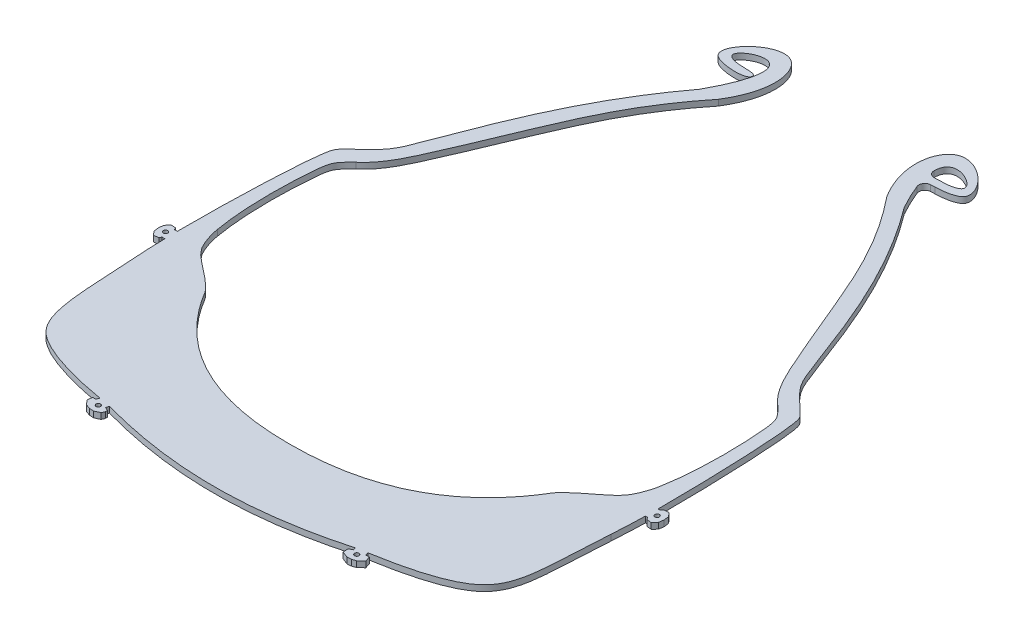
SolidWorks part; units mm, degrees
ref_plane "Front Plane" through (0, 0, 0) normal (0, 0, 1) x (1, 0, 0)
ref_plane "Top Plane" through (0, 0, 0) normal (0, 1, 0) x (1, 0, 0)
ref_plane "Right Plane" through (0, 0, 0) normal (1, 0, 0) x (0, 0, -1)
sketch "Sketch1" plane through (0, 0, 0) normal (0, 1, 0) x (1, 0, 0)
  line L0 (-56.7342, 4649.685) -> (-54.3432, 4649.8666)
  line L1 (-54.3432, 4649.8666) -> (-51.9673, 4650.1279)
  line L2 (-51.9673, 4650.1279) -> (-49.6128, 4650.4904)
  line L3 (-49.6128, 4650.4904) -> (-47.2873, 4650.9763)
  line L4 (-47.2873, 4650.9763) -> (-45.0028, 4651.606)
  line L5 (-45.0028, 4651.606) -> (-42.7754, 4652.393)
  line L6 (-42.7754, 4652.393) -> (-40.6236, 4653.3398)
  line L7 (-40.6236, 4653.3398) -> (-38.5569, 4654.4471)
  line L8 (-38.5569, 4654.4471) -> (-36.5628, 4655.7048)
  line L9 (-36.5628, 4655.7048) -> (-34.628, 4657.0886)
  line L10 (-34.628, 4657.0886) -> (-32.7572, 4658.5809)
  line L11 (-32.7572, 4658.5809) -> (-31.8781, 4659.3559)
  line L12 (-31.8781, 4659.3559) -> (-31.0378, 4660.1663)
  line L13 (-31.0378, 4660.1663) -> (-30.2434, 4661.0133)
  line L14 (-30.2434, 4661.0133) -> (-29.4929, 4661.8977)
  line L15 (-29.4929, 4661.8977) -> (-28.0377, 4663.8002)
  line L16 (-28.0377, 4663.8002) -> (-26.6418, 4665.7643)
  line L17 (-26.6418, 4665.7643) -> (-25.2842, 4667.7433)
  line L18 (-25.2842, 4667.7433) -> (-24.5616, 4668.7671)
  line L19 (-24.5616, 4668.7671) -> (-24.1207, 4669.3049)
  line L20 (-24.1207, 4669.3049) -> (-23.6287, 4669.8041)
  line L21 (-23.6287, 4669.8041) -> (-22.6527, 4670.6453)
  line L22 (-22.6527, 4670.6453) -> (-21.6624, 4671.4168)
  line L23 (-21.6624, 4671.4168) -> (-19.7154, 4672.8766)
  line L24 (-19.7154, 4672.8766) -> (-18.7888, 4673.6051)
  line L25 (-18.7888, 4673.6051) -> (-17.9151, 4674.3646)
  line L26 (-17.9151, 4674.3646) -> (-17.0961, 4675.1711)
  line L27 (-17.0961, 4675.1711) -> (-16.3332, 4676.0235)
  line L28 (-16.3332, 4676.0235) -> (-14.888, 4677.8872)
  line L29 (-14.888, 4677.8872) -> (-14.2651, 4678.8282)
  line L30 (-14.2651, 4678.8282) -> (-13.7395, 4679.8092)
  line L31 (-13.7395, 4679.8092) -> (-13.3157, 4680.8364)
  line L32 (-13.3157, 4680.8364) -> (-12.9921, 4681.9053)
  line L33 (-12.9921, 4681.9053) -> (-12.765, 4683.0137)
  line L34 (-12.765, 4683.0137) -> (-12.6116, 4684.156)
  line L35 (-12.6116, 4684.156) -> (-12.4221, 4686.5439)
  line L36 (-12.4221, 4686.5439) -> (-12.3049, 4688.9547)
  line L37 (-12.3049, 4688.9547) -> (-12.23, 4691.3606)
  line L38 (-12.23, 4691.3606) -> (-12.2173, 4693.7469)
  line L39 (-12.2173, 4693.7469) -> (-12.2979, 4696.128)
  line L40 (-12.2979, 4696.128) -> (-12.4621, 4698.525)
  line L41 (-12.4621, 4698.525) -> (-12.9016, 4703.3562)
  line L42 (-12.9016, 4703.3562) -> (-13.1725, 4705.7323)
  line L43 (-13.1725, 4705.7323) -> (-13.359, 4706.8497)
  line L44 (-13.359, 4706.8497) -> (-13.6464, 4707.8976)
  line L45 (-13.6464, 4707.8976) -> (-13.8331, 4708.3435)
  line L46 (-13.8331, 4708.3435) -> (-14.0727, 4708.7863)
  line L47 (-14.0727, 4708.7863) -> (-14.3603, 4709.2104)
  line L48 (-14.3603, 4709.2104) -> (-14.6922, 4709.6118)
  line L49 (-14.6922, 4709.6118) -> (-15.5352, 4710.4427)
  line L50 (-15.5352, 4710.4427) -> (-16.4733, 4711.2489)
  line L51 (-16.4733, 4711.2489) -> (-18.3969, 4712.8768)
  line L52 (-18.3969, 4712.8768) -> (-19.3317, 4713.7593)
  line L53 (-19.3317, 4713.7593) -> (-19.7964, 4714.2738)
  line L54 (-19.7964, 4714.2738) -> (-20.226, 4714.8564)
  line L55 (-20.226, 4714.8564) -> (-20.8491, 4716.0227)
  line L56 (-20.8491, 4716.0227) -> (-21.3607, 4717.2182)
  line L57 (-21.3607, 4717.2182) -> (-22.2565, 4719.6128)
  line L58 (-22.2565, 4719.6128) -> (-23.9365, 4724.4003)
  line L59 (-23.9365, 4724.4003) -> (-24.8142, 4726.6925)
  line L60 (-24.8142, 4726.6925) -> (-25.7235, 4728.951)
  line L61 (-25.7235, 4728.951) -> (-29.4192, 4737.978)
  line L62 (-29.4192, 4737.978) -> (-31.3112, 4742.476)
  line L63 (-31.3112, 4742.476) -> (-32.3108, 4744.6883)
  line L64 (-32.3108, 4744.6883) -> (-33.3653, 4746.8748)
  line L65 (-33.3653, 4746.8748) -> (-34.484, 4749.0197)
  line L66 (-34.484, 4749.0197) -> (-35.6822, 4751.1089)
  line L67 (-35.6822, 4751.1089) -> (-36.9697, 4753.1376)
  line L68 (-36.9697, 4753.1376) -> (-38.335, 4755.1176)
  line L69 (-38.335, 4755.1176) -> (-39.7566, 4757.0561)
  line L70 (-39.7566, 4757.0561) -> (-41.2239, 4758.9538)
  line L71 (-41.2239, 4758.9538) -> (-44.2837, 4762.6862)
  line L72 (-44.2837, 4762.6862) -> (-45.0093, 4763.5782)
  line L73 (-45.7102, 4766.0333) -> (-45.6003, 4766.895)
  line L74 (-44.3387, 4767.2717) -> (-41.5099, 4763.9631)
  line L75 (-41.5099, 4763.9631) -> (-39.7615, 4761.7893)
  line L76 (-39.7615, 4761.7893) -> (-36.1552, 4757.1077)
  line L77 (-36.1552, 4757.1077) -> (-34.4224, 4754.6956)
  line L78 (-34.4224, 4754.6956) -> (-32.818, 4752.1875)
  line L79 (-32.818, 4752.1875) -> (-31.4001, 4749.5854)
  line L80 (-31.4001, 4749.5854) -> (-30.1172, 4746.945)
  line L81 (-30.1172, 4746.945) -> (-27.7453, 4741.6402)
  line L82 (-27.7453, 4741.6402) -> (-25.4835, 4736.2816)
  line L83 (-25.4835, 4736.2816) -> (-23.2904, 4730.8724)
  line L84 (-23.2904, 4730.8724) -> (-21.1708, 4725.4153)
  line L85 (-21.1708, 4725.4153) -> (-19.1018, 4719.943)
  line L86 (-19.1018, 4719.943) -> (-18.1004, 4717.2034)
  line L87 (-18.1004, 4717.2034) -> (-17.875, 4716.5966)
  line L88 (-17.875, 4716.5966) -> (-17.6236, 4716.1359)
  line L89 (-17.6236, 4716.1359) -> (-17.2675, 4715.7336)
  line L90 (-17.2675, 4715.7336) -> (-16.7845, 4715.2999)
  line L91 (-16.7845, 4715.2999) -> (-14.566, 4713.4273)
  line L92 (-14.566, 4713.4273) -> (-13.4359, 4712.453)
  line L93 (-13.4359, 4712.453) -> (-12.2875, 4711.3506)
  line L94 (-12.2875, 4711.3506) -> (-11.7288, 4710.5494)
  line L95 (-11.7288, 4710.5494) -> (-11.4049, 4709.6505)
  line L96 (-11.4049, 4709.6505) -> (-11.1035, 4708.0976)
  line L97 (-11.1035, 4708.0976) -> (-10.7039, 4705.1867)
  line L98 (-10.7039, 4705.1867) -> (-10.3782, 4702.2301)
  line L99 (-10.3782, 4702.2301) -> (-10.1381, 4699.312)
  line L100 (-10.1381, 4699.312) -> (-9.9526, 4696.4059)
  line L101 (-9.9526, 4696.4059) -> (-9.8234, 4693.4642)
  line L102 (-9.8234, 4693.4642) -> (-9.7818, 4690.5097)
  line L103 (-9.7818, 4690.5097) -> (-9.8395, 4687.5651)
  line L104 (-9.8395, 4687.5651) -> (-10.1467, 4681.8499)
  line L105 (-10.2187, 4680.4106) -> (-10.5778, 4674.8324)
  line L106 (-10.5778, 4674.8324) -> (-10.9255, 4669.1921)
  line L107 (-10.9255, 4669.1921) -> (-11.1085, 4666.3239)
  line L108 (-11.1085, 4666.3239) -> (-11.3672, 4663.3976)
  line L109 (-11.3672, 4663.3976) -> (-11.5954, 4661.8877)
  line L110 (-11.5954, 4661.8877) -> (-11.9481, 4660.3817)
  line L111 (-11.9481, 4660.3817) -> (-12.469, 4658.9063)
  line L112 (-12.469, 4658.9063) -> (-13.1768, 4657.5086)
  line L113 (-13.1768, 4657.5086) -> (-14.0475, 4656.2056)
  line L114 (-14.0475, 4656.2056) -> (-15.0678, 4655.0233)
  line L115 (-15.0678, 4655.0233) -> (-15.6664, 4654.4674)
  line L116 (-15.6664, 4654.4674) -> (-16.3022, 4653.9611)
  line L117 (-16.3022, 4653.9611) -> (-17.6055, 4653.1269)
  line L118 (-17.6055, 4653.1269) -> (-18.9712, 4652.4383)
  line L119 (-18.9712, 4652.4383) -> (-20.3502, 4651.8561)
  line L120 (-20.3502, 4651.8561) -> (-21.7405, 4651.3486)
  line L121 (-21.7405, 4651.3486) -> (-23.1491, 4650.8937)
  line L122 (-23.1491, 4650.8937) -> (-25.9685, 4650.1281)
  line L123 (-25.9685, 4650.1281) -> (-28.8127, 4649.495)
  line L124 (-28.8127, 4649.495) -> (-34.3611, 4648.4388)
  line L125 (-35.7786, 4648.1905) -> (-42.1243, 4647.1501)
  line L126 (-42.1243, 4647.1501) -> (-45.3893, 4646.7207)
  line L127 (-45.3893, 4646.7207) -> (-48.6635, 4646.3827)
  line L128 (-48.6635, 4646.3827) -> (-55.1892, 4645.922)
  line L129 (-55.1892, 4645.922) -> (-61.7354, 4645.5886)
  line L130 (-61.7354, 4645.5886) -> (-63.9666, 4645.5453)
  line L131 (-63.9667, 4649.4865) -> (-59.1315, 4649.5688)
  line L132 (-59.1315, 4649.5688) -> (-56.7342, 4649.685)
  line L133 (-9.7721, 4681.8294) -> (-9.752, 4682.186)
  line L134 (-9.752, 4682.186) -> (-9.3693, 4682.5229)
  line L135 (-9.3693, 4682.5229) -> (-8.649, 4682.4768)
  line L136 (-8.649, 4682.4768) -> (-7.9775, 4681.713)
  line L137 (-7.9775, 4681.713) -> (-8.2411, 4680.2884)
  line L138 (-8.2411, 4680.2884) -> (-9.0059, 4679.6162)
  line L139 (-9.0059, 4679.6162) -> (-9.5491, 4679.6473)
  line L140 (-9.5491, 4679.6473) -> (-9.8867, 4680.0303)
  line L141 (-9.8867, 4680.0303) -> (-9.8664, 4680.3889)
  line L142 (-9.7721, 4681.8294) -> (-9.752, 4682.186)
  line L151 (-34.2991, 4648.0806) -> (-33.9447, 4648.1421)
  line L152 (-33.9447, 4648.1421) -> (-33.5285, 4647.8485)
  line L153 (-33.5285, 4647.8485) -> (-33.4056, 4647.1395)
  line L154 (-33.4056, 4647.1395) -> (-33.9931, 4646.3074)
  line L155 (-33.9931, 4646.3074) -> (-35.4108, 4646.0612)
  line L156 (-35.4108, 4646.0612) -> (-36.2441, 4646.6493)
  line L157 (-36.2441, 4646.6493) -> (-36.3669, 4647.358)
  line L158 (-36.3669, 4647.358) -> (-36.0733, 4647.7743)
  line L159 (-36.0733, 4647.7743) -> (-35.7187, 4647.8357)
  line L160 (-10.1467, 4681.8499) -> (-9.7721, 4681.8294)
  line L161 (-34.3611, 4648.4388) -> (-34.2991, 4648.0806)
  line L162 (-35.7786, 4648.1905) -> (-35.7187, 4647.8357)
  line L163 (-9.8664, 4680.3889) -> (-10.2187, 4680.4106)
  line L165 (-118.1813, 4682.186) -> (-118.5641, 4682.5226)
  line L166 (-118.5641, 4682.5226) -> (-119.2843, 4682.4768)
  line L167 (-119.2843, 4682.4768) -> (-119.9558, 4681.7128)
  line L168 (-119.9558, 4681.7128) -> (-119.8643, 4680.2786)
  line L169 (-119.8643, 4680.2786) -> (-119.0995, 4679.6064)
  line L170 (-119.0995, 4679.6064) -> (-118.3843, 4679.6471)
  line L171 (-118.3843, 4679.6471) -> (-118.0466, 4680.0303)
  line L172 (-118.0466, 4680.0303) -> (-118.0672, 4680.3889)
  line L173 (-118.0672, 4680.3889) -> (-117.7148, 4680.4103)
  line L174 (-117.7148, 4680.4103) -> (-117.3555, 4674.8322)
  line L175 (-117.3555, 4674.8322) -> (-117.0078, 4669.1921)
  line L176 (-117.0078, 4669.1921) -> (-116.8249, 4666.3237)
  line L177 (-116.8249, 4666.3237) -> (-116.566, 4663.3974)
  line L178 (-116.566, 4663.3974) -> (-116.3378, 4661.8875)
  line L179 (-116.3378, 4661.8875) -> (-115.9851, 4660.3817)
  line L180 (-115.9851, 4660.3817) -> (-115.4645, 4658.906)
  line L181 (-115.4645, 4658.906) -> (-114.7563, 4657.5086)
  line L182 (-114.7563, 4657.5086) -> (-113.8857, 4656.2053)
  line L183 (-113.8857, 4656.2053) -> (-112.8656, 4655.0233)
  line L184 (-112.8656, 4655.0233) -> (-112.2669, 4654.4674)
  line L185 (-112.2669, 4654.4674) -> (-111.6311, 4653.9608)
  line L186 (-111.6311, 4653.9608) -> (-110.328, 4653.1269)
  line L187 (-110.328, 4653.1269) -> (-108.9621, 4652.4383)
  line L188 (-108.9621, 4652.4383) -> (-107.5832, 4651.8561)
  line L189 (-107.5832, 4651.8561) -> (-106.1928, 4651.3484)
  line L190 (-106.1928, 4651.3484) -> (-104.7844, 4650.8937)
  line L191 (-104.7844, 4650.8937) -> (-101.9649, 4650.1279)
  line L192 (-101.9649, 4650.1279) -> (-99.1205, 4649.4948)
  line L193 (-99.1205, 4649.4948) -> (-93.5721, 4648.4388)
  line L194 (-93.5721, 4648.4388) -> (-93.6341, 4648.0806)
  line L195 (-93.6341, 4648.0806) -> (-93.9885, 4648.1421)
  line L196 (-93.9885, 4648.1421) -> (-94.4046, 4647.8485)
  line L197 (-94.4046, 4647.8485) -> (-94.5276, 4647.1392)
  line L198 (-94.5276, 4647.1392) -> (-93.9404, 4646.3074)
  line L199 (-93.9404, 4646.3074) -> (-92.5223, 4646.0612)
  line L200 (-92.5223, 4646.0612) -> (-91.6891, 4646.6493)
  line L201 (-91.6891, 4646.6493) -> (-91.5662, 4647.358)
  line L202 (-91.5662, 4647.358) -> (-91.8598, 4647.7743)
  line L203 (-91.8598, 4647.7743) -> (-92.2145, 4647.8357)
  line L204 (-92.1546, 4648.1905) -> (-92.2145, 4647.8357)
  line L205 (-92.1546, 4648.1905) -> (-85.8089, 4647.1501)
  line L206 (-85.8089, 4647.1501) -> (-82.5441, 4646.7204)
  line L207 (-82.5441, 4646.7204) -> (-79.2698, 4646.3827)
  line L208 (-79.2698, 4646.3827) -> (-72.7439, 4645.922)
  line L209 (-72.7439, 4645.922) -> (-66.1978, 4645.5886)
  line L210 (-66.1978, 4645.5886) -> (-63.9666, 4645.5453)
  line L211 (-63.9667, 4649.4865) -> (-68.8018, 4649.5688)
  line L212 (-68.8018, 4649.5688) -> (-71.1991, 4649.685)
  line L213 (-71.1991, 4649.685) -> (-73.5901, 4649.8666)
  line L214 (-73.5901, 4649.8666) -> (-75.9659, 4650.1279)
  line L215 (-75.9659, 4650.1279) -> (-78.3204, 4650.4904)
  line L216 (-78.3204, 4650.4904) -> (-80.646, 4650.976)
  line L217 (-80.646, 4650.976) -> (-82.9304, 4651.606)
  line L218 (-82.9304, 4651.606) -> (-85.1578, 4652.393)
  line L219 (-85.1578, 4652.393) -> (-87.3097, 4653.3398)
  line L220 (-87.3097, 4653.3398) -> (-89.3762, 4654.4469)
  line L221 (-89.3762, 4654.4469) -> (-91.3704, 4655.7045)
  line L222 (-91.3704, 4655.7045) -> (-93.3054, 4657.0883)
  line L223 (-93.3054, 4657.0883) -> (-95.1761, 4658.5809)
  line L224 (-95.1761, 4658.5809) -> (-96.0551, 4659.3559)
  line L225 (-96.0551, 4659.3559) -> (-96.8955, 4660.1661)
  line L226 (-96.8955, 4660.1661) -> (-97.6899, 4661.013)
  line L227 (-97.6899, 4661.013) -> (-98.4405, 4661.8974)
  line L228 (-98.4405, 4661.8974) -> (-99.8956, 4663.8003)
  line L229 (-99.8956, 4663.8003) -> (-101.2917, 4665.7643)
  line L230 (-101.2917, 4665.7643) -> (-102.649, 4667.7433)
  line L231 (-102.649, 4667.7433) -> (-103.3717, 4668.7671)
  line L232 (-103.3717, 4668.7671) -> (-103.8126, 4669.3049)
  line L233 (-103.8126, 4669.3049) -> (-104.3045, 4669.8038)
  line L234 (-104.3045, 4669.8038) -> (-105.2805, 4670.645)
  line L235 (-105.2805, 4670.645) -> (-106.2711, 4671.4168)
  line L236 (-106.2711, 4671.4168) -> (-108.218, 4672.8766)
  line L237 (-108.218, 4672.8766) -> (-109.1446, 4673.6051)
  line L238 (-109.1446, 4673.6051) -> (-110.0184, 4674.3646)
  line L239 (-110.0184, 4674.3646) -> (-110.8371, 4675.1711)
  line L240 (-110.8371, 4675.1711) -> (-111.6001, 4676.0232)
  line L241 (-111.6001, 4676.0232) -> (-113.0454, 4677.8872)
  line L242 (-113.0454, 4677.8872) -> (-113.6683, 4678.8282)
  line L243 (-113.6683, 4678.8282) -> (-114.1938, 4679.8092)
  line L244 (-114.1938, 4679.8092) -> (-114.6176, 4680.8364)
  line L245 (-114.6176, 4680.8364) -> (-114.9413, 4681.905)
  line L246 (-114.9413, 4681.905) -> (-115.1684, 4683.0135)
  line L247 (-115.1684, 4683.0135) -> (-115.3218, 4684.156)
  line L248 (-115.3218, 4684.156) -> (-115.5115, 4686.5436)
  line L249 (-115.5115, 4686.5436) -> (-115.6283, 4688.9545)
  line L250 (-115.6283, 4688.9545) -> (-115.7033, 4691.3606)
  line L251 (-115.7033, 4691.3606) -> (-115.7161, 4693.7466)
  line L252 (-115.7161, 4693.7466) -> (-115.6355, 4696.1278)
  line L253 (-115.6355, 4696.1278) -> (-115.4714, 4698.525)
  line L254 (-115.4714, 4698.525) -> (-115.0316, 4703.3562)
  line L255 (-115.0316, 4703.3562) -> (-114.7608, 4705.732)
  line L256 (-114.7608, 4705.732) -> (-114.5743, 4706.8497)
  line L257 (-114.5743, 4706.8497) -> (-114.287, 4707.8977)
  line L258 (-114.287, 4707.8977) -> (-114.1002, 4708.3435)
  line L259 (-114.1002, 4708.3435) -> (-113.8608, 4708.7862)
  line L260 (-113.8608, 4708.7862) -> (-113.5731, 4709.2103)
  line L261 (-113.5731, 4709.2103) -> (-113.2411, 4709.6117)
  line L262 (-113.2411, 4709.6117) -> (-112.3981, 4710.4425)
  line L263 (-112.3981, 4710.4425) -> (-111.4599, 4711.2487)
  line L264 (-111.4599, 4711.2487) -> (-109.5364, 4712.8767)
  line L265 (-109.5364, 4712.8767) -> (-108.602, 4713.7592)
  line L266 (-108.602, 4713.7592) -> (-108.1369, 4714.2737)
  line L267 (-108.1369, 4714.2737) -> (-107.7072, 4714.8564)
  line L268 (-107.7072, 4714.8564) -> (-107.0842, 4716.0225)
  line L269 (-107.0842, 4716.0225) -> (-106.5727, 4717.2181)
  line L270 (-106.5727, 4717.2181) -> (-105.6769, 4719.6127)
  line L271 (-105.6769, 4719.6127) -> (-103.9969, 4724.4001)
  line L272 (-103.9969, 4724.4001) -> (-103.1193, 4726.6924)
  line L273 (-103.1193, 4726.6924) -> (-102.2099, 4728.9509)
  line L274 (-102.2099, 4728.9509) -> (-98.5143, 4737.9778)
  line L275 (-98.5143, 4737.9778) -> (-96.6221, 4742.4757)
  line L276 (-96.6221, 4742.4757) -> (-95.6227, 4744.6884)
  line L277 (-95.6227, 4744.6884) -> (-94.5682, 4746.8748)
  line L278 (-94.5682, 4746.8748) -> (-93.4493, 4749.0197)
  line L279 (-93.4493, 4749.0197) -> (-92.2515, 4751.1088)
  line L280 (-92.2515, 4751.1088) -> (-90.9637, 4753.1374)
  line L281 (-90.9637, 4753.1374) -> (-89.5985, 4755.1174)
  line L282 (-89.5985, 4755.1174) -> (-88.177, 4757.0561)
  line L283 (-88.177, 4757.0561) -> (-86.7094, 4758.9538)
  line L284 (-86.7094, 4758.9538) -> (-83.65, 4762.6862)
  line L285 (-83.65, 4762.6862) -> (-82.924, 4763.5782)
  line L286 (-82.2232, 4766.0334) -> (-82.3333, 4766.8949)
  line L287 (-83.5948, 4767.2716) -> (-86.4235, 4763.963)
  line L288 (-86.4235, 4763.963) -> (-88.172, 4761.7894)
  line L289 (-88.172, 4761.7894) -> (-91.7784, 4757.1074)
  line L290 (-91.7784, 4757.1074) -> (-93.5112, 4754.6958)
  line L291 (-93.5112, 4754.6958) -> (-95.1154, 4752.1875)
  line L292 (-95.1154, 4752.1875) -> (-96.5333, 4749.5852)
  line L293 (-96.5333, 4749.5852) -> (-97.8162, 4746.9449)
  line L294 (-97.8162, 4746.9449) -> (-100.1881, 4741.6403)
  line L295 (-100.1881, 4741.6403) -> (-102.4501, 4736.2814)
  line L296 (-102.4501, 4736.2814) -> (-104.6429, 4730.8726)
  line L297 (-104.6429, 4730.8726) -> (-106.7626, 4725.415)
  line L298 (-106.7626, 4725.415) -> (-108.8314, 4719.9429)
  line L299 (-108.8314, 4719.9429) -> (-109.8329, 4717.2035)
  line L300 (-109.8329, 4717.2035) -> (-110.0583, 4716.5964)
  line L301 (-110.0583, 4716.5964) -> (-110.3097, 4716.1357)
  line L302 (-110.3097, 4716.1357) -> (-110.6661, 4715.7335)
  line L303 (-110.6661, 4715.7335) -> (-111.1489, 4715.2998)
  line L304 (-111.1489, 4715.2998) -> (-113.3676, 4713.4272)
  line L305 (-113.3676, 4713.4272) -> (-114.4976, 4712.4528)
  line L306 (-114.4976, 4712.4528) -> (-115.646, 4711.3505)
  line L307 (-115.646, 4711.3505) -> (-116.2044, 4710.5493)
  line L308 (-116.2044, 4710.5493) -> (-116.5286, 4709.6504)
  line L309 (-116.5286, 4709.6504) -> (-116.8298, 4708.0975)
  line L310 (-116.8298, 4708.0975) -> (-117.2296, 4705.1868)
  line L311 (-117.2296, 4705.1868) -> (-117.5553, 4702.2301)
  line L312 (-117.5553, 4702.2301) -> (-117.7952, 4699.312)
  line L313 (-117.7952, 4699.312) -> (-117.981, 4696.4059)
  line L314 (-117.981, 4696.4059) -> (-118.11, 4693.4642)
  line L315 (-118.11, 4693.4642) -> (-118.1516, 4690.5097)
  line L316 (-118.1516, 4690.5097) -> (-118.0939, 4687.5649)
  line L317 (-118.0939, 4687.5649) -> (-117.7865, 4681.8497)
  line L318 (-117.7865, 4681.8497) -> (-118.1612, 4681.8294)
  line L319 (-118.1612, 4681.8294) -> (-118.1813, 4682.186)
  spline S0 degree 3 poles (-45.7102, 4766.0333) (-45.8224, 4765.1537) (-45.5692, 4764.2663) (-45.0093, 4763.5782) knots 0 0 0 0 1 1 1 1
  spline S1 degree 3 poles (-44.3387, 4767.2717) (-44.5973, 4767.574) (-45.0517, 4767.6095) (-45.3539, 4767.351) knots 0 0 0 0 1 1 1 1
  spline S2 degree 3 poles (-45.3539, 4767.351) (-45.4898, 4767.2349) (-45.5777, 4767.0723) (-45.6003, 4766.895) knots 0 0 0 0 1 1 1 1
  spline S3 degree 3 poles (-82.924, 4763.5782) (-82.3642, 4764.2661) (-82.111, 4765.1536) (-82.2232, 4766.0334) knots 0 0 0 0 1 1 1 1
  spline S4 degree 3 poles (-82.3333, 4766.8949) (-82.3835, 4767.2894) (-82.7441, 4767.5683) (-83.1386, 4767.518) knots 0 0 0 0 1 1 1 1
  spline S5 degree 3 poles (-83.1386, 4767.518) (-83.3159, 4767.4954) (-83.4785, 4767.4075) (-83.5948, 4767.2716) knots 0 0 0 0 1 1 1 1
sketch "Sketch2" plane through (0, 0, 0) normal (0, 1, 0) x (1, 0, 0)
  line L0 (-63.9234, 4631.4262) -> (-63.9234, 4609.4594) construction
  line L25 (-22.4985, 4637.3551) -> (-18.9434, 4638.0357) construction
  line L26 (-20.7209, 4637.6954) -> (-20.3316, 4635.6618) construction
  line L31 (-16.9423, 4635.297) -> (-18.5347, 4633.796)
  line L32 (-20.3316, 4635.6618) -> (-19.8467, 4633.1287) construction
  line L33 (-18.5347, 4633.796) -> (-19.8873, 4633.3404)
  line L34 (-21.3125, 4633.2642) -> (-19.8873, 4633.3404)
  line L35 (-23.3466, 4634.071) -> (-21.3125, 4633.2642)
  line L40 (-104.4735, 4635.7404) -> (-104.4735, 4634.9567)
  line L41 (-104.4735, 4634.9567) -> (-104.8805, 4633.998)
  line L42 (-104.8805, 4633.998) -> (-106.6203, 4633.1744)
  line L43 (-106.6203, 4633.1744) -> (-108.2043, 4633.2927)
  line L44 (-109.6975, 4633.8343) -> (-108.2043, 4633.2927)
  line L45 (-110.9466, 4635.2989) -> (-109.6975, 4633.8343)
  line L46 (-110.9246, 4636.3402) -> (-110.9466, 4635.2989)
  line L47 (-110.6737, 4637.0191) -> (-110.9246, 4636.3402)
  line L49 (-146.8202, 4697.6298) -> (-149.3915, 4697.5949) construction
  line L50 (16.9036, 4697.658) -> (18.9735, 4697.6298) construction
  line L54 (20.0716, 4700.6062) -> (21.1812, 4699.2558)
  line L55 (18.9735, 4697.6298) -> (21.5448, 4697.5949) construction
  line L56 (21.1812, 4699.2558) -> (21.376, 4697.5972)
  line L57 (21.1362, 4695.9445) -> (21.376, 4697.5972)
  line L58 (19.9903, 4694.6247) -> (21.1362, 4695.9445)
  line L62 (-144.7504, 4697.658) -> (-146.8202, 4697.6298) construction
  line L67 (-148.983, 4695.9445) -> (-149.2228, 4697.5972)
  line L68 (-149.028, 4699.2558) -> (-149.2228, 4697.5972)
  line L69 (-147.9184, 4700.6062) -> (-149.028, 4699.2558)
  line L73 (18.4279, 4700.4703) -> (20.0716, 4700.6062)
  line L74 (18.3509, 4694.8052) -> (19.9903, 4694.6247)
  line L75 (-23.4805, 4635.8657) -> (-23.3466, 4634.071)
  line L76 (-17.4807, 4637.0143) -> (-16.9423, 4635.297)
  line L77 (-32.2984, 4843.1108) -> (-32.9734, 4843.0745)
  line L78 (-30.1329, 4840.4892) -> (-31.6175, 4840.4173)
  line L79 (-146.2747, 4700.4703) -> (-146.0774, 4699.7908)
  line L80 (-146.0774, 4699.7908) -> (-144.9978, 4699.7908)
  line L81 (-146.1977, 4694.8052) -> (-145.9394, 4695.5191)
  line L82 (-145.9394, 4695.5191) -> (-144.9397, 4695.5191)
  line L83 (-110.6737, 4637.0191) -> (-109.7005, 4637.0191)
  line L84 (-109.7005, 4637.0191) -> (-109.3372, 4638.0212)
  line L85 (-104.4735, 4635.7404) -> (-105.6297, 4636.1595)
  line L86 (-105.6297, 4636.1595) -> (-105.3482, 4637.2394)
  line L87 (-23.4805, 4635.8657) -> (-22.2692, 4636.4725)
  line L88 (-22.2692, 4636.4725) -> (-22.4985, 4637.3551)
  line L89 (-17.4807, 4637.0143) -> (-18.7231, 4637.0143)
  line L90 (-18.7231, 4637.0143) -> (-18.9434, 4638.0357)
  line L91 (17.093, 4695.5191) -> (17.927, 4695.5191)
  line L92 (17.927, 4695.5191) -> (18.3509, 4694.8052)
  line L93 (17.151, 4699.7908) -> (17.9273, 4699.7908)
  line L94 (17.9273, 4699.7908) -> (18.4279, 4700.4703)
  line L95 (-147.9184, 4700.6062) -> (-146.2747, 4700.4703)
  line L96 (-148.983, 4695.9445) -> (-147.9184, 4694.6247)
  line L97 (-147.9184, 4694.6247) -> (-146.1977, 4694.8052)
  circle A0 centre (28.2666, 4698.0399) radius 0.5
  circle A1 centre (-20.3316, 4635.6618) radius 0.75
  circle A2 centre (-107.5151, 4635.6618) radius 0.75
  circle A4 centre (18.9735, 4697.6298) radius 0.75
  circle A5 centre (-146.8202, 4697.6298) radius 0.75
  arc A6 (-33.3889, 4837.7057) -> (-31.6175, 4840.4173) centre (-31.5206, 4838.4196) cw
  arc A7 (-35.0807, 4845.0881) -> (-32.9734, 4843.0745) centre (-33.0807, 4845.0716) ccw
  spline S0 degree 3 poles (-105.3482, 4637.2394) (-91.774, 4633.4496) (-63.9165, 4629.3481) (-36.075, 4633.5591) (-22.4985, 4637.3551) knots 0.018742 0.018742 0.018742 0.018742 0.500293 0.981945 0.981945 0.981945 0.981945
  spline S1 degree 3 poles (-18.9434, 4638.0357) (-9.0248, 4639.6859) (4.6467, 4643.0604) (16.372, 4654.3944) (15.2524, 4666.3346) (16.6172, 4684.5147) knots 0.018902 0.018902 0.018902 0.018902 0.394122 0.490995 0.987629 0.987629 0.987629 0.987629
  spline S2 degree 3 poles (16.6172, 4684.5147) (16.7593, 4687.5885) (17.0552, 4691.3248) (17.093, 4695.5191) knots 0.004735 0.004735 0.004735 0.004735 0.035162 0.035162 0.035162 0.035162
  spline S3 degree 3 poles (17.151, 4699.7908) (17.187, 4718.7532) (15.9463, 4748.1489) (12.9962, 4752.2096) (5.5902, 4758.1445) (-2.0809, 4776.0395) (-10.7699, 4804.5442) (-29.3841, 4829.3082) knots 0.04445 0.04445 0.04445 0.04445 0.175223 0.204985 0.326837 0.407861 1 1 1 1
  spline S4 degree 2 poles (-63.9234, 4656.5726) (-23.3221, 4656.4521) (-5.293, 4686.6697) knots 0 0 0 1 1 1
  spline S5 degree 3 poles (-5.293, 4686.6697) (-3.3882, 4689.5147) (5.5322, 4695.6316) (7.0158, 4697.627) (8.9185, 4699.9572) (10.6489, 4704.6448) (10.9298, 4707.0618) knots 0 0 0 0 0.517385 0.711984 0.762678 1 1 1 1
  spline S6 degree 3 poles (10.9298, 4707.0618) (12.5257, 4715.666) (12.951, 4730.9053) (11.2091, 4746.2487) (8.6834, 4748.7091) (7.186, 4750.111) knots 0 0 0 0 0.7977 0.8977 1 1 1 1
  spline S7 degree 3 poles (7.186, 4750.111) (2.646, 4753.9155) (-14.478, 4791.0238) (-18.8641, 4808.8265) (-35.5523, 4829.6542) knots 0 0 0 0 0.147118 0.925748 0.925748 0.925748 0.925748
  spline S8 degree 3 poles (-29.3841, 4829.3082) (-30.2798, 4830.9279) (-31.829, 4833.9406) (-32.9356, 4836.5196) (-33.3889, 4837.7057) knots 0 0 0 0 0.008449 0.016898 0.016898 0.016898 0.016898
  spline S9 degree 3 poles (-98.4627, 4829.3082) (-93.3382, 4838.5746) (-89.9132, 4854.9965) (-105.7569, 4846.1357) (-99.8483, 4842.6646) (-93.6101, 4843.6599) (-92.6055, 4839.7881) (-104.6155, 4840.3686) (-107.728, 4847.4621) (-89.6554, 4862.6974) (-85.2547, 4840.9598) (-92.2945, 4829.6542) knots 0 0 0 0 0.048335 0.142928 0.16216 0.231927 0.259382 0.409256 0.461524 0.763332 1 1 1 1
  spline S10 degree 3 poles (-135.0327, 4750.111) (-130.4928, 4753.9155) (-113.3687, 4791.0238) (-108.9827, 4808.8265) (-92.2945, 4829.6542) knots 0 0 0 0 0.147118 0.925748 0.925748 0.925748 0.925748
  spline S11 degree 3 poles (-138.7766, 4707.0618) (-140.3724, 4715.666) (-140.7978, 4730.9053) (-139.0558, 4746.2487) (-136.5302, 4748.7091) (-135.0327, 4750.111) knots 0 0 0 0 0.7977 0.8977 1 1 1 1
  spline S12 degree 3 poles (-122.5537, 4686.6697) (-124.4586, 4689.5147) (-133.3789, 4695.6316) (-134.8625, 4697.627) (-136.7653, 4699.9572) (-138.4957, 4704.6448) (-138.7766, 4707.0618) knots 0 0 0 0 0.517385 0.711984 0.762678 1 1 1 1
  spline S13 degree 2 poles (-63.9234, 4656.5726) (-104.5246, 4656.4521) (-122.5537, 4686.6697) knots 0 0 0 1 1 1
  spline S14 degree 3 poles (-144.7494, 4689.4807) (-144.8339, 4691.3079) (-144.8968, 4693.3424) (-144.9397, 4695.5191) knots 0.004735 0.004735 0.004735 0.004735 0.022822 0.022822 0.022822 0.022822
  spline S15 degree 3 poles (-109.3372, 4638.0212) (-119.1435, 4639.6853) (-132.6028, 4643.2518) (-144.26, 4654.2895) (-143.3596, 4671.4378) (-144.7494, 4689.4807) knots 0.024856 0.024856 0.024856 0.024856 0.394717 0.491493 0.992616 0.992616 0.992616 0.992616
  spline S16 degree 3 poles (-35.0807, 4845.0881) (-35.0748, 4845.7931) (-34.0801, 4852.841) (-22.3331, 4846.3093) (-27.0864, 4843.0688) (-30.5037, 4843.2073) (-32.2984, 4843.1108) knots 0.039445 0.039445 0.039445 0.039445 0.048335 0.142928 0.159173 0.210778 0.210778 0.210778 0.210778
  spline S17 degree 3 poles (-30.1329, 4840.4892) (-27.3481, 4840.4868) (-22.5863, 4841.4479) (-20.6493, 4847.6968) (-38.0996, 4862.695) (-42.5921, 4840.9598) (-35.5523, 4829.6542) knots 0.329046 0.329046 0.329046 0.329046 0.418095 0.461524 0.763332 1 1 1 1
  spline S18 degree 3 poles (-144.9978, 4699.7908) (-145.1407, 4717.9008) (-143.9805, 4747.7816) (-140.9459, 4752.3433) (-133.5185, 4758.0955) (-125.8345, 4776.2473) (-117.0769, 4804.5442) (-98.4627, 4829.3082) knots 0.034256 0.034256 0.034256 0.034256 0.174203 0.204985 0.326837 0.407861 1 1 1 1
  dimension "D1" = 1
  dimension "D2" = 2
extrude "Boss-Extrude2" add sketch "Sketch2" along normal blind 2 separate body contours S15 S0 S1 S2 S8 S7 S6 S5 S4 S13 S12 S11 S10 region at (-19.6622, 0, -4636.5872)
